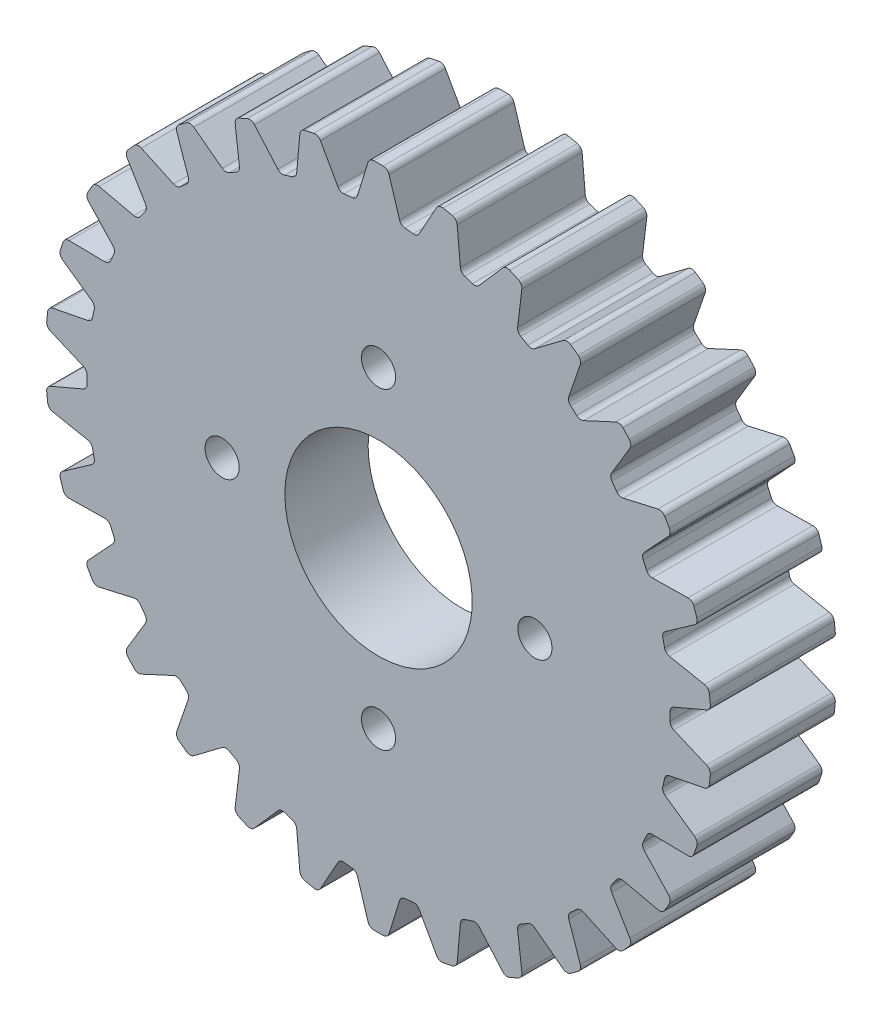
SolidWorks part; units mm, degrees
ref_plane "Front Plane" through (0, 0, 0) normal (0, 0, 1) x (1, 0, 0)
ref_plane "Top Plane" through (0, 0, 0) normal (0, 1, 0) x (1, 0, 0)
ref_plane "Right Plane" through (0, 0, 0) normal (1, 0, 0) x (0, 0, -1)
sketch "Sketch1" plane through (0, 0, 0) normal (0, 0, 1) x (1, 0, 0)
  circle A2 centre (0, 0) radius 14
  dimension "Blank diameter" = 28
extrude "Body" add sketch "Sketch1" against normal blind 6
sketch "Sketch2" plane through (0, 0, 0) normal (0, 0, 1) x (1, 0, 0)
  line L0 (0, 26.3446) -> (0, 3.6554) construction
  line L1 (-0.755, 14.981) -> (-1.0697, 13.9591)
  line L2 (-0.755, 14.981) -> (-0.4431, 15.9939)
  line L3 (0.755, 14.981) -> (1.0697, 13.9591)
  line L4 (0.755, 14.981) -> (0.4431, 15.9939)
  line L5 (0, 0) -> (-2.2254, 44.1563) construction
  line L6 (0, 0) -> (2.1494, 42.6484) construction
  arc A0 (0.4431, 15.9939) -> (-0.4431, 15.9939) centre (0, 0) ccw
  arc A1 (0.755, 14.981) -> (-0.755, 14.981) centre (0, 0) ccw construction
  arc A2 (1.0697, 13.9591) -> (-1.0697, 13.9591) centre (0, 0) ccw
  point P1 (0, 15)
  dimension "D2" = 20
  dimension "D3" = 20
  dimension "Full diameter" = 32
  dimension "Pitch diameter" = 30
  dimension "Blank diameter" = 28
  dimension "Tooth width PCD" = 1.51
extrude "Tooth" add sketch "Sketch2" against normal blind 6
fillet "Tooth Fillet" radius 0.3 4 edges at (-0.4431, 15.9939, -3) (-1.0697, 13.9591, -3) (0.4431, 15.9939, -3) (1.0697, 13.9591, -3)
pattern_circular "Tooth Pattern" count 30 over 360 about axis through (0, 0, 0) along (0, 0, 1) of "Tooth", "Tooth Fillet"
ref_axis "Axis1" through (0, 0, 0) along (0, 0, -1)
sketch "Sketch3" plane through (0, 0, 0) normal (0, 0, 1) x (1, 0, 0)
  circle A0 centre (0, 0) radius 5.25
  circle A1 centre (0, 0) radius 12
  dimension "Plastic boss" = 10.5
  dimension "Resses" = 24
extrude "Resses1" [suppressed] cut sketch "Sketch3" against normal blind 1
sketch "Sketch4" plane through (0, 0, -6) normal (0, 0, -1) x (-1, 0, 0)
  circle A0 centre (0, 0) radius 12
  circle A1 centre (0, 0) radius 5.25
  dimension "Plastic boss" = 10.5
  dimension "Resses" = 24
extrude "Resses2" cut sketch "Sketch4" against normal blind 1
sketch "Sketch5" plane through (0, 0, -6) normal (0, 0, -1) x (-1, 0, 0)
  circle A0 centre (0, 0) radius 5
  dimension "D1" = 10
extrude "Brass boss" [suppressed] add sketch "Sketch5" along normal blind 5.7
sketch "Sketch6" [suppressed] plane through (0, 0, -11.7) normal (0, 0, -1) x (-1, 0, 0)
  circle A0 centre (0, 0) radius 2
  dimension "D1" = 4
extrude "Bore" [suppressed] cut sketch "Sketch6" against normal through all
sketch "Sketch7" plane through (0, 0, 0) normal (0, 1, 0) x (1, 0, 0)
  circle A0 centre (0, 8.8626) radius 1
  dimension "D1" = 2
extrude "Grub screw" [suppressed] cut sketch "Sketch7" against normal through all
sketch "Sketch8" plane through (0, 0, -5) normal (0, 0, -1) x (-1, 0, 0)
  circle A0 centre (-0.8321, 10.5608) radius 1.8434
extrude "Extrude1" [suppressed] add sketch "Sketch8" along normal blind 5
sketch "Sketch9" plane through (0, 0, -6) normal (0, 0, -1) x (-1, 0, 0)
  circle A0 centre (0, 0) radius 10.75
  dimension "D1" = 21.5
extrude "Cut-Extrude1" cut sketch "Sketch9" against normal blind 2
sketch "Sketch10" plane through (0, 0, -6) normal (0, 0, -1) x (-1, 0, 0)
  circle A0 centre (0, 0) radius 10.75 construction
  circle A1 centre (0, 0) radius 10.75
  circle A2 centre (0, 0) radius 12.75
  dimension "D1" = 2
extrude "Boss-Extrude1" add sketch "Sketch10" against normal up to surface (6 mm away) up to face at (0, 0, 0)
sketch "Sketch11" plane through (0, 0, -4) normal (0, 0, -1) x (-1, 0, 0)
  circle A0 centre (0, 0) radius 4.5
  circle A1 centre (0, 7.51) radius 0.82
  circle A2 centre (7.51, 0) radius 0.82
  circle A3 centre (0, -7.51) radius 0.82
  circle A4 centre (-7.51, 0) radius 0.82
  point P14 (0, 0)
  dimension "D1" = 9
  dimension "D2" = 1.64
  dimension "D3" = 7.51
  dimension "D4" = 4
extrude "Cut-Extrude2" cut sketch "Sketch11" against normal through all
